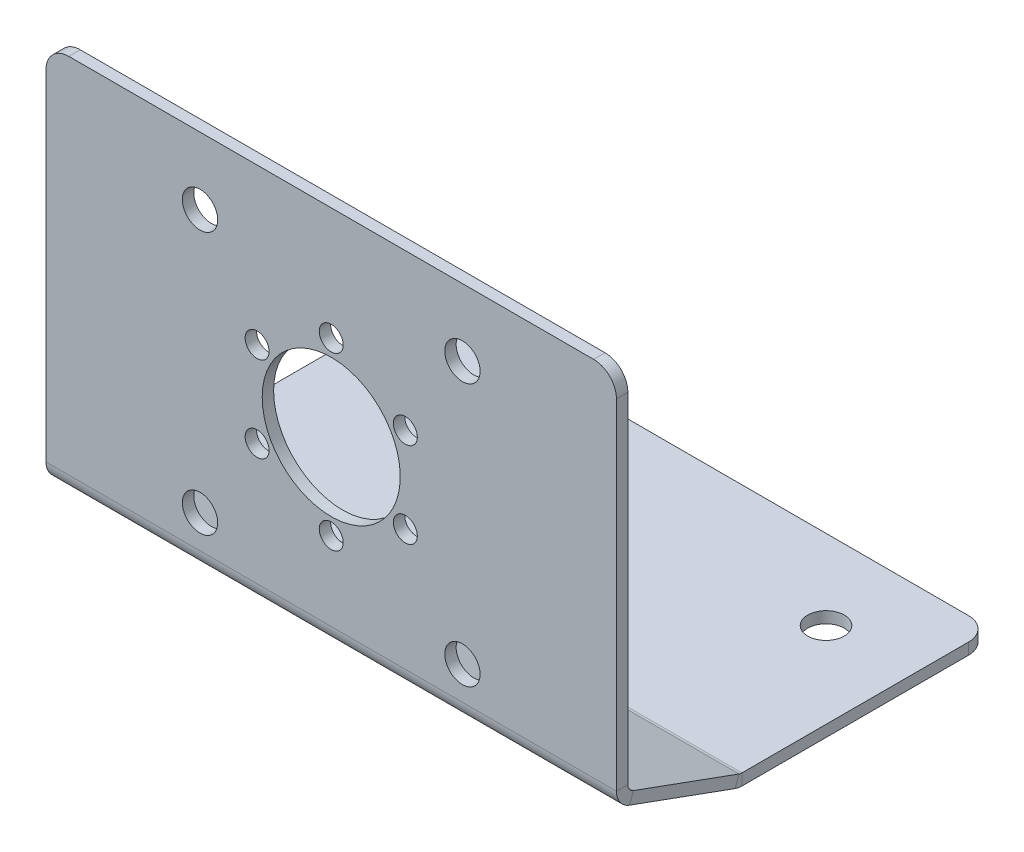
SolidWorks part; units mm, degrees
note: The reader was unsure of these and kept them because the rebuilt part matched: flange length of "边线-法兰5", "边线-法兰4".
ref_plane "前视基准面" through (0, 0, 0) normal (0, 0, 1) x (1, 0, 0)
ref_plane "上视基准面" through (0, 0, 0) normal (0, 1, 0) x (1, 0, 0)
ref_plane "右视基准面" through (0, 0, 0) normal (1, 0, 0) x (0, 0, -1)
sketch "草图1" plane through (0, 0, 0) normal (0, 1, 0) x (1, 0, 0)
  line L1 (-25, 11) -> (25, 11)
  line L2 (-25, 11) -> (-25, -11)
  line L3 (-25, -11) -> (25, -11)
  line L4 (25, 11) -> (25, -11)
  line L5 (0, -11) -> (0, 11) construction
  line L6 (-25, 0) -> (25, 0) construction
  circle A0 centre (0, -7.5) radius 1.6
  circle A2 centre (-17.5, 4) radius 1.6
  circle A3 centre (17.5, 4) radius 1.6
  point P0 (0, 0)
  dimension "D3" = 3.2
  dimension "D7" = 3.2
  dimension "D1" = 50
  dimension "D2" = 22
  dimension "D4" = 3.5
  dimension "D5" = 15
  dimension "D6" = 7.5
base flange "基体-法兰1" sketch "草图1" thickness 1 reverse thickness direction no parameters "D1"=0.7366
edge flange "边线-法兰5" sketch "草图21" flange angle 160 flange length 10.5 flange position material outside bend radius 0.7366 thickness 1 relief rectangular parameters "D6"=10
sketch "草图21" plane through (0, 0, 11) normal (0, -0.9397, 0.342) x (1, 0, 0)
  line L0 (-25, 0) -> (25, 0) construction
  line L1 (-25, 0) -> (25, 0)
  line L2 (-25, 0) -> (-25, 10.5)
  line L3 (-25, 10.5) -> (25, 10.5)
  line L4 (25, 10.5) -> (25, 0)
bend "边线折弯5" bend radius 0.7366 bend angle 20 parameters "D5"=1
edge flange "边线-法兰4" sketch "草图23" flange angle 110 flange length 33 flange position material outside bend radius 0.7366 thickness 1 relief rectangular parameters "D6"=10
bend "边线折弯6" bend radius 0.7366 bend angle 70 parameters "D5"=2
sketch "草图23" plane through (0, 3.5912, 20.8668) normal (0, 0, 1) x (1, 0, 0)
  line L0 (25, 0) -> (-25, 0) construction
  line L1 (25, 0) -> (-25, 0)
  line L2 (-25, 0) -> (-25, 32.2998)
  line L3 (-25, 32.2998) -> (25, 32.2998)
  line L4 (25, 32.2998) -> (25, 0)
sketch "草图9" plane through (0, 0, 20.8668) normal (0, 0, -1) x (-1, 0, 0)
  line L1 (-11.5, 30) -> (11.5, 30) construction
  line L2 (-11.5, 30) -> (-11.5, 7) construction
  line L3 (-11.5, 7) -> (11.5, 7) construction
  line L4 (11.5, 30) -> (11.5, 7) construction
  line L5 (0, 7) -> (0, 30) construction
  line L6 (-11.5, 18.5) -> (11.5, 18.5) construction
  line L7 (0, 35.891) -> (0, 4.107) construction
  line L8 (-25, 35.891) -> (25, 35.891) construction
  line L9 (25, 4.107) -> (-25, 4.107) construction
  line L10 (-25, -1) -> (25, -1) construction
  circle A0 centre (0, 18.5) radius 6.05
  circle A1 centre (0, 18.5) radius 7.5 construction
  circle A2 centre (0, 26) radius 1.05
  circle A8 centre (-11.5, 30) radius 1.55
  circle A9 centre (-11.5, 7) radius 1.55
  circle A10 centre (11.5, 7) radius 1.55
  circle A11 centre (11.5, 30) radius 1.55
  circle A12 centre (0, 18.5) radius 4.1 construction
  circle A13 centre (6.4952, 22.25) radius 1.05
  circle A14 centre (6.4952, 14.75) radius 1.05
  circle A15 centre (0, 11) radius 1.05
  circle A16 centre (-6.4952, 14.75) radius 1.05
  circle A17 centre (-6.4952, 22.25) radius 1.05
  point P9 (0, 0)
  point P10 (0, 0)
  point P18 (0, 0)
  point P39 (0, 18.5)
  point P40 (0, 0)
  dimension "D2" = 12.1
  dimension "D3" = 15
  dimension "D4" = 2.1
  dimension "D6" = 3.1
  dimension "D7" = 3.1
  dimension "D8" = 3.1
  dimension "D9" = 3.1
  dimension "D10" = 8.2
  dimension "D5" = 23
  dimension "D11" = 8
  dimension "D13" = 6
extrude "切除-拉伸1" cut sketch "草图9" against normal blind 10 contours A8 | A11 | A13 | A2 | A17 | A16 | A15 | A14 | A0 A12 | A12 | A10 | A9 normal cut yes
fillet "圆角1" radius 2 4 edges at (25, -0.5, -11) (-25, -0.5, -11) (25, 35.891, 21.3668) (-25, 35.891, 21.3668)
sketch "折弯-线1" plane through (0, 0, 0) normal (0, 1, 0) x (1, 0, 0)
sketch "边界框1" plane through (0, 0, 0) normal (0, 1, 0) x (1, 0, 0)
sheet metal parameters "钣金6" thickness 1 parameters "D1"=0.7366
flat pattern "平板型式6" [suppressed]
sketch "折弯-线2" plane through (0, 0, 0) normal (0, 1, 0) x (1, 0, 0)
sketch "边界框2" [suppressed] plane through (0, 0, 0) normal (0, 1, 0) x (1, 0, 0)
sheet metal parameters "钣金8" thickness 1 parameters "D1"=0.7366
flat pattern "平板型式6" [suppressed]
sketch "折弯-线2" plane through (0, 0, 0) normal (0, 1, 0) x (1, 0, 0)
sketch "边界框2" [suppressed] plane through (0, 0, 0) normal (0, 1, 0) x (1, 0, 0)
bend of the flat pattern "展平-<边线折弯5>3"
bend of the flat pattern "展平-<边线折弯6>2"
sheet metal parameters "钣金10" thickness 1 parameters "D1"=0.7366
flat pattern "平板型式6" [suppressed]
sketch "折弯-线2"
sketch "边界框2" [suppressed]
bend of the flat pattern "展平-<边线折弯5>2"
bend of the flat pattern "展平-<边线折弯6>1"
sheet metal parameters "钣金11" thickness 1 parameters "D1"=0.7366
flat pattern "平板型式6" [suppressed]
sketch "折弯-线2"
sketch "边界框2" [suppressed]
bend of the flat pattern "展平-<边线折弯5>1"
